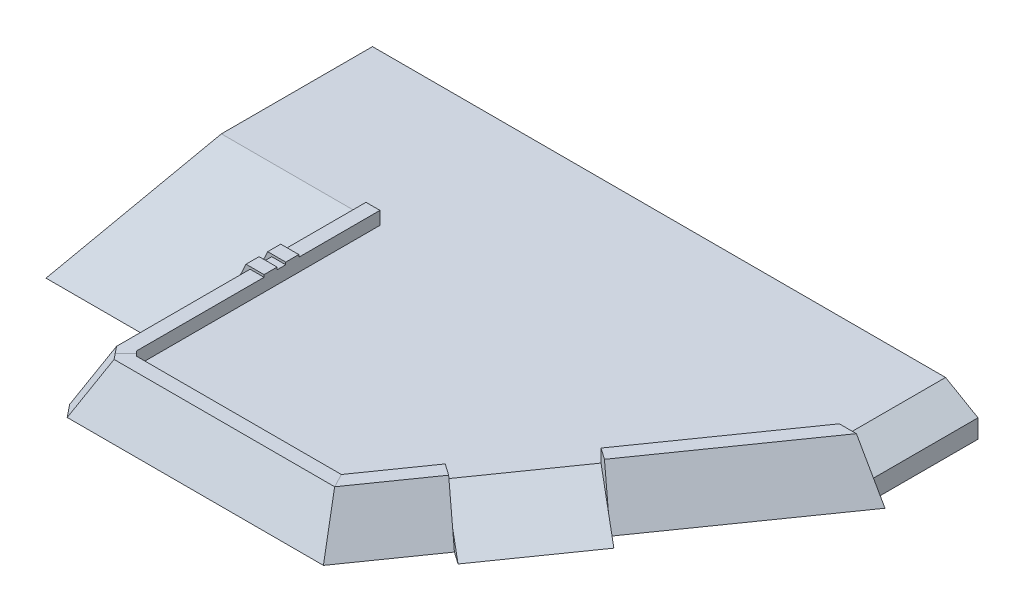
SolidWorks part; units mm, degrees
ref_plane "前视基准面" through (0, 0, 0) normal (0, 0, 1) x (1, 0, 0)
ref_plane "上视基准面" through (0, 0, 0) normal (0, 1, 0) x (1, 0, 0)
ref_plane "右视基准面" through (0, 0, 0) normal (1, 0, 0) x (0, 0, -1)
sketch "草图1" plane through (0, 0, 0) normal (0, 1, 0) x (1, 0, 0)
  line L0 (0, 0) -> (6148, 0)
  line L1 (6148, 0) -> (6148, -1140.0744)
  line L2 (6148, -1140.0744) -> (3948, -4282)
  line L3 (3948, -4282) -> (1701, -4282)
  line L4 (1701, -4282) -> (1701, -1621)
  line L5 (1701, -1621) -> (0, -1621)
  line L6 (0, -1621) -> (0, 0)
  dimension "D1" = 6148
  dimension "D2" = 1621
  dimension "D3" = 4282
  dimension "D4" = 4447
  dimension "D5" = 125
  dimension "D6" = 2247
extrude "凸台-拉伸1" add sketch "草图1" along normal blind 400
sketch "草图2" plane through (1701, 0, 0) normal (-1, 0, 0) x (0, 0, 1)
  line L0 (1621, 400) -> (3502.852, 0)
  line L1 (1621, 0) -> (4282, 0) construction
  line L2 (3502.852, 0) -> (1621, 0)
  line L3 (1621, 0) -> (1621, 400)
  dimension "D1" = 12
extrude "凸台-拉伸2" add sketch "草图2" along normal up to surface (1701 mm away) up to face at (0, 200, 810.5)
ref_plane "基准面1" through (0, 0, 3282) normal (0, 0, 1) x (1, 0, 0)
sketch "草图3" plane through (0, 0, 0) normal (0, 0, -1) x (-1, 0, 0)
  line L0 (-6148, 400) -> (-6148, 0)
  line L1 (-6148, 0) -> (0, 0) construction
  line L2 (-6148, 400) -> (-6148, 0) construction
  line L3 (-6148, 0) -> (-6840.8203, 0)
  line L4 (-6840.8203, 0) -> (-6148, 400)
  dimension "D1" = 30
extrude "凸台-拉伸3" add sketch "草图3" against normal up to vertex (1140.0744 mm away) up to point (6148, 400, 1140.0744)
sketch "草图4" plane through (0, 0, 3282) normal (0, 0, 1) x (1, 0, 0)
  line L0 (1701, 400) -> (1701, 539.3929)
  line L1 (1701, 539.3929) -> (1551, 539.3929)
  line L4 (1551, 539.3929) -> (1299.4769, 0)
  line L5 (0, 0) -> (1701, 0) construction
  line L6 (1299.4769, 0) -> (1701, 0)
  line L7 (1701, 0) -> (1701, 400)
  line L12 (0, 400) -> (1486, 400) construction
  line L13 (0, 400) -> (1701, 400) construction
  dimension "D1" = 150
  dimension "D2" = 1486
  dimension "D3" = 65
sketch "草图5" plane through (0, 400, 0) normal (0, 1, 0) x (1, 0, 0)
  line L0 (1701, -1621) -> (1701, -4282)
  line L1 (1701, -3502.852) -> (1701, -1621) construction
  line L2 (1701, -1621) -> (1701, -4282) construction
  line L3 (1701, -4282) -> (3948, -4282)
  line L4 (3948, -4282) -> (6434.7882, -730.4984)
  line L7 (0, -1621) -> (1701, -1621) construction
  line L8 (3948, -4282) -> (6148, -1140.0744) construction
  line L9 (1701, -4282) -> (3948, -4282) construction
  dimension "D1" = 500
sweep "扫描2" add profiles "草图4" path "草图5"
sketch "草图6" plane through (0, 0, 0) normal (0, 0, -1) x (-1, 0, 0)
  line L0 (-6148, 400) -> (-6148, 600)
  line L1 (-6148, 600) -> (-6840.8203, 600)
  line L2 (-6840.8203, 600) -> (-6840.8203, 0)
  line L3 (-6840.8203, 0) -> (-6148, 400)
  dimension "D1" = 200
extrude "切除-拉伸1" cut sketch "草图6" against normal up to surface (1140.0744 mm away) up to face at (6672.6496, 58.0932, 1140.0744)
chamfer "倒角1" distance 100 angle 45 1 edges at (1425.2385, 269.6965, 4557.7615) first distance on face at (2758.3954, 269.6965, 4557.7615)
chamfer "倒角2" distance 50 angle 45 1 edges at (1701, 469.6965, 4282)
sketch "草图7" plane through (0, 0, 1621) normal (0, 0, -1) x (-1, 0, 0)
  line L0 (-1701, 0) -> (-1701, 564.3929)
  line L1 (-1701, 564.3929) -> (-1507.4888, 564.3929)
  line L2 (-1507.4888, 564.3929) -> (-1244.308, 0)
  line L3 (2355.1, 0) -> (-2355.1, 0) construction
  line L4 (-1244.308, 0) -> (-1701, 0)
  line L5 (-1551, 539.3929) -> (-1486, 400) construction
  line L6 (-1701, 539.3929) -> (-1551, 539.3929) construction
  point P11 (-1626, 539.3929)
  dimension "D1" = 50
  dimension "D2" = 25
extrude "凸台-拉伸4" add sketch "草图7" against normal blind 140 from offset 870.9 offset against normal yes
pattern_linear "阵列(线性)1" count 2 spacing 232.7 along (0, 0, 1) of "凸台-拉伸4"
ref_plane "基准面3" through (3948, 539.3929, 4282) normal (-0.5736, 0, 0.8192) x (0.8192, 0, 0.5736)
sketch "草图8" plane through (3948, 539.3929, 4282) normal (-0.5736, 0, 0.8192) x (0.8192, 0, 0.5736)
  line L0 (0, -139.3929) -> (560.7793, -539.3929)
  line L1 (560.7793, -539.3929) -> (0, -539.3929)
  line L2 (0, -539.3929) -> (0, -139.3929)
  line L3 (320.2552, -365.1135) -> (0, -139.3929) construction
  line L4 (0, -139.3929) -> (0, 0) construction
  line L5 (0, -139.3929) -> (0, 260.6071)
  line L6 (0, 260.6071) -> (560.7793, -539.3929)
  dimension "D1" = 35.5
  dimension "D2" = 400
extrude "凸台-拉伸5" add sketch "草图8" against normal blind 1200 from offset 800 contours L2 L1 L0 region at (4101.1212, 133.3333, 4389.2166) offset against normal yes
extrude "切除-拉伸2" cut sketch "草图8<3>" against normal blind 1200 from offset 800 contours L6 L5 L0 region at (4101.1212, 400, 4389.2166) offset against normal yes
sketch "草图8<3>" plane through (3948, 539.3929, 4282) normal (-0.5736, 0, 0.8192) x (0.8192, 0, 0.5736) same geometry as "草图8"
sketch "草图9" plane through (0, 0, 0) normal (1, 0, 0) x (0, 0, -1)
  line L0 (2575.9377, 0) -> (-2575.9377, 0) construction
  line L1 (-1140.0744, 400) -> (0, 400)
  line L2 (-1140.0744, 400) -> (-1140.0744, 0)
  line L3 (-1140.0744, 0) -> (0, 0)
  line L4 (0, 400) -> (0, 0)
  line L5 (-570.0372, 0) -> (-570.0372, 400) construction
  line L6 (-1140.0744, 200) -> (0, 200) construction
  line L7 (0, 310.4161) -> (0, -310.4161) construction
  line L8 (-1140.0744, 400) -> (0, 400) construction
  line L9 (-1140.0744, 174.2795) -> (-1140.0744, 400) construction
  line L10 (-1140.0744, 174.2795) -> (-1140.0744, 539.3929) construction
  point P0 (-570.0372, 200)
extrude "切除-拉伸3" cut sketch "草图9" against normal blind 345 from vertex starting at point (6840.8203, 0, 0)
